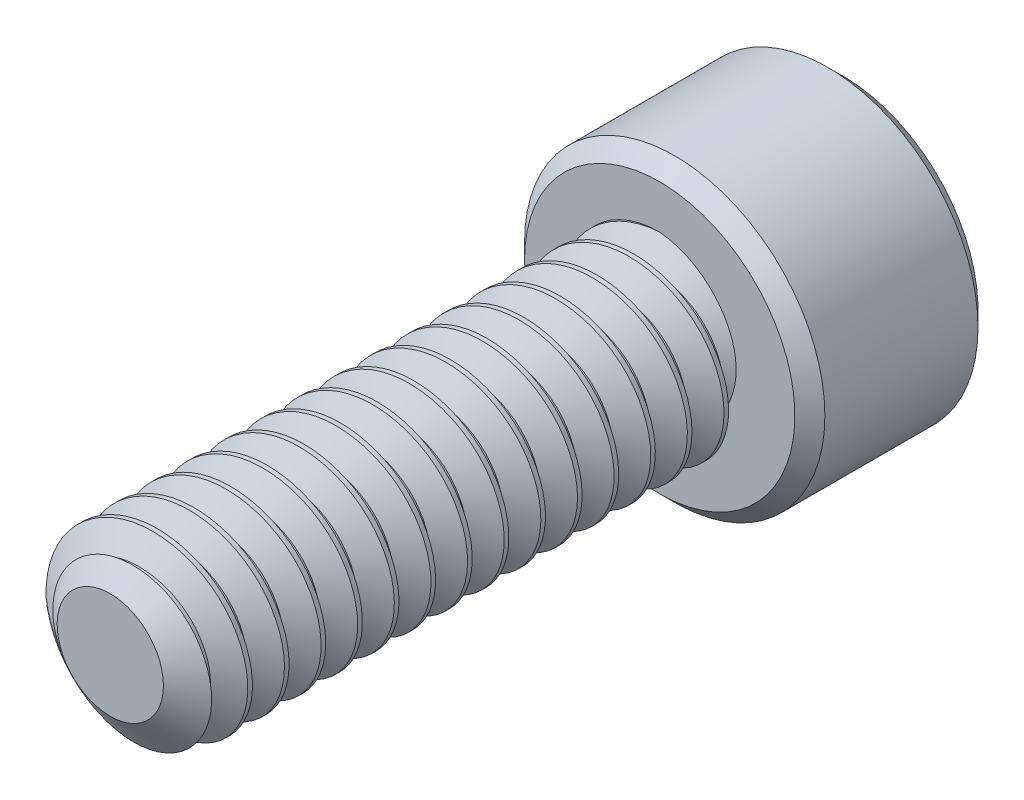
SolidWorks part; units mm, degrees
other "DetailItem1"
ref_plane "Front Plane" through (0, 0, 0) normal (0, 0, 1) x (1, 0, 0)
ref_plane "Top Plane" through (0, 0, 0) normal (0, 1, 0) x (1, 0, 0)
ref_plane "Right Plane" through (0, 0, 0) normal (1, 0, 0) x (0, 0, -1)
sketch "Sketch1" plane through (0, 0, 0) normal (0, 0, 1) x (1, 0, 0)
  circle A0 centre (0, 0) radius 1.5875
  dimension "OD" = 3.175
extrude "Extrude1" add sketch "Sketch1" against normal blind 9.525
sketch "Sketch2" plane through (0, 0, 0) normal (0, 0, 1) x (1, 0, 0)
  circle A0 centre (0, 0) radius 1.5875 construction
  circle A1 centre (0, 0) radius 1.5875
curve "Helix/Spiral1" pitch 0.635 height 10.16 radius 1.5875 centre (0, 0, 0) axis (0, 0, -1) start towards (0, 1, 0) parameters "pitch"=0.635
sketch "Sketch3" plane through (0, 0, 0) normal (1, 0, 0) x (0, 0, -1)
  line L0 (-0.5556, 1.5875) -> (-0.3175, 1.1751)
  line L1 (-0.3175, 1.1751) -> (-0.2381, 1.1751)
  line L2 (-0.2381, 1.1751) -> (0, 1.5875)
  line L3 (-0.5556, 1.5875) -> (0, 1.5875)
  line L4 (-0.2778, 1.5875) -> (-0.2778, 1.1751) construction
  line L5 (-0.4366, 1.3813) -> (-0.1191, 1.3813) construction
  line L6 (0, 1.5875) -> (0, -1.5875) construction
  dimension "D1" = 0.0794
  dimension "D2" = 0.3175
  dimension "D3" = 60
sweep "Cut-Sweep1" cut profiles "Sketch3" path "Helix/Spiral1"
sketch "Sketch4" plane through (0, 0, 0) normal (1, 0, 0) x (0, 0, -1)
  line L0 (0.4666, 1.5875) -> (0, 0.9211)
  line L1 (0, 0.9211) -> (0, 1.5875)
  line L2 (0.4666, 1.5875) -> (0, 1.5875)
  line L3 (-0.5556, 1.5875) -> (0, 1.5875) construction
  line L4 (0, 0) -> (7.0209, 0) construction
  dimension "D1" = 55
  dimension "D2" = 0.254
revolve "Cut-Revolve1" cut sketch "Sketch4" angle 360 about L4
sketch "Sketch5" plane through (0, 0, 0) normal (1, 0, 0) x (0, 0, -1)
  line L0 (9.525, -1.1864) -> (9.525, 1.1327) construction
  line L1 (9.525, 1.7145) -> (0.1202, 1.7145)
  line L2 (9.525, 1.7145) -> (9.525, 0)
  line L3 (9.525, 0) -> (0, 0)
  line L4 (0, 1.3843) -> (0, 0)
  line L5 (0.1202, 1.7145) -> (0, 1.3843)
  line L6 (0, 0) -> (9.9695, 0) construction
  point P3 (0, 1.7145)
  point P10 (0, 1.7145)
  dimension "D1" = 0.3302
  dimension "D2" = 0.127
  dimension "D3" = 20
  dimension "Min Thread" = 0
revolve "partially thread" [suppressed] add sketch "Sketch5" angle 360 about L6
sketch "Sketch6" plane through (0, 0, -9.525) normal (0, 0, -1) x (-1, 0, 0)
  circle A0 centre (0, 0) radius 2.6035
  dimension "head dia" = 5.207
extrude "Extrude2" add sketch "Sketch6" along normal blind 3.175
sketch "Sketch7" plane through (0, 0, -12.7) normal (0, 0, -1) x (-1, 0, 0)
  line L1 (0, 1.3748) -> (-1.1906, 0.6874)
  line L2 (-1.1906, 0.6874) -> (-1.1906, -0.6874)
  line L3 (-1.1906, -0.6874) -> (0, -1.3748)
  line L4 (0, -1.3748) -> (1.1906, -0.6874)
  line L5 (1.1906, -0.6874) -> (1.1906, 0.6874)
  line L6 (1.1906, 0.6874) -> (0, 1.3748)
  circle A0 centre (0, 0) radius 1.1906 construction
  dimension "hex dia" = 2.3813
extrude "Cut-Extrude1" cut sketch "Sketch7" against normal blind 1.7859
sketch "Sketch8" plane through (0, 0, -12.7) normal (0, 0, -1) x (-1, 0, 0)
  circle A0 centre (0, 0) radius 1.3748
extrude "Cut-Extrude2" cut sketch "Sketch8" against normal through all draft 45
chamfer "Chamfer1" distance 0.2604 angle 45 2 edges at (-2.6035, 0, -12.7) (-2.6035, 0, -9.525)
sketch "Sketch9" plane through (0, 0, 0) normal (1, 0, 0) x (0, 0, -1)
  line L0 (0, 1.5875) -> (0, -1.5875) construction
  line L1 (1.5875, 1.5875) -> (1.5875, -1.5875) construction
  dimension "D1" = 1.5875
  dimension "D4" = 0.635
  dimension "D5" = 0.3302
equation "\"D3@Helix/Spiral1\" = \"screw length@Extrude1\"+\"pitch@Helix/Spiral1\""
equation "\"D1@Sketch3\" = \"pitch@Helix/Spiral1\"*.125"
equation "\"D2@Sketch3\" = \"pitch@Helix/Spiral1\"*.5"
equation "\"D1@Cut-Extrude1\" = \"hex dia@Sketch7\"*.75"
equation "\"D1@Chamfer1\" = \"head dia@Sketch6\"*.05"
equation "\"D1@Sketch9\" = \"pitch@Helix/Spiral1\"*2.5"
